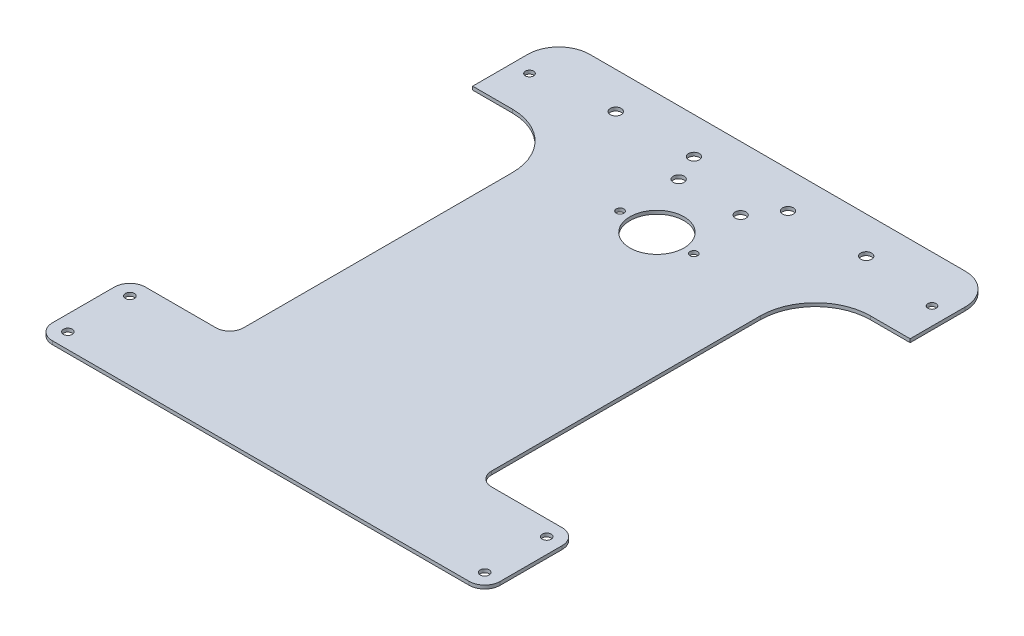
SolidWorks part; units mm, degrees
material "Thornel VCB-20 Carbon Cloth"
ref_plane "Front" through (0, 0, 0) normal (0, 0, 1) x (1, 0, 0)
ref_plane "Top" through (0, 0, 0) normal (0, 1, 0) x (1, 0, 0)
ref_plane "Right" through (0, 0, 0) normal (1, 0, 0) x (0, 0, -1)
ref_axis "X" through (-80.9, 0, 0) along (1, 0, 0)
ref_axis "Y" through (0, -50, 0) along (0, 1, 0)
ref_axis "Z" through (0, 0, -80.9) along (0, 0, 1)
sketch "Sketch1" plane through (0, 0, 0) normal (0, 1, 0) x (1, 0, 0)
  line L0 (-65, -150) -> (65, -150)
  line L1 (-65, -150) -> (-65, -123)
  line L2 (-65, -123) -> (-36, -123)
  line L3 (-36, -123) -> (-36, -25)
  line L4 (-36, -25) -> (-63.5, -25)
  line L5 (-63.5, -25) -> (-63.5, 0)
  line L6 (-63.5, 0) -> (63.5, 0)
  line L7 (63.5, 0) -> (63.5, -25)
  line L8 (63.5, -25) -> (36, -25)
  line L9 (36, -25) -> (36, -123)
  line L10 (36, -123) -> (65, -123)
  line L11 (65, -123) -> (65, -150)
  line L12 (0, -150) -> (0, 0) construction
  dimension "D1" = 130
  dimension "D2" = 72
  dimension "D5" = 25
  dimension "D6" = 127
  dimension "D7" = 150
  dimension "D3" = 27
  dimension "D4" = 90
extrude "Boss-Extrude1" add sketch "Sketch1" along normal mid plane 1
hole_wizard "M2 Clearance Hole1" positions "Sketch2" profile "Sketch3" hole size "M2" standard "ANSI Metric" end condition up to next
sketch "Sketch2" plane through (0, 0.5, 0) normal (0, 1, 0) x (1, 0, 0)
  line L0 (-60.5, -145.5) -> (60.5, -145.5) construction
  line L2 (-65, -150) -> (65, -150) construction
  line L3 (-65, -123) -> (-65, -150) construction
  line L4 (65, -150) -> (65, -123) construction
  line L5 (-60.5, -127.5) -> (-60.5, -145.5) construction
  line L8 (60.5, -127.5) -> (60.5, -145.5) construction
  point P0 (-60.5, -145.5)
  point P2 (60.5, -145.5)
  point P15 (-60.5, -127.5)
  point P17 (60.5, -127.5)
  dimension "D1" = 4.5
  dimension "D2" = 4.5
  dimension "D3" = 4.5
  dimension "D4" = 18
sketch "Sketch3" plane through (-60.5, 0.5, 145.5) normal (1, 0, 0) x (0, 0, 1)
  line L0 (0, 0) -> (0, 1)
  line L1 (0, 1) -> (1.3, 1)
  line L2 (1.3, 1) -> (1.3, 0)
  line L5 (1.3, 0) -> (0, 0)
  line L11 (0, -6.35) -> (0, 107.95) construction
  dimension "Thru Hole Dia." = 2.6
  dimension "Thru Hole Depth" = 1
fillet "Fillet1" radius 4.5 4 edges at (65, 0, 150) (-65, 0, 150) (65, 0, 123) (-65, 0, 123)
fillet "Fillet2" radius 9 2 edges at (63.5, 0, 0) (-63.5, 0, 0)
hole_wizard "M2 Clearance Hole2" positions "Sketch7" profile "Sketch8" hole size "M2" standard "ANSI Metric" end condition up to next
sketch "Sketch7" plane through (0, 0.5, 0) normal (0, 1, 0) x (1, 0, 0)
  line L0 (-58.42, -13.57) -> (58.42, -13.57) construction
  line L2 (0, 0) -> (0, -13.57) construction
  line L3 (54.5, 0) -> (-54.5, 0) construction
  line L5 (-63.5, -25) -> (-36, -25) construction
  point P0 (-58.42, -13.57)
  point P2 (58.42, -13.57)
  dimension "D1" = 116.84
  dimension "D2" = 11.43
sketch "Sketch8" plane through (-58.42, 0.5, 13.57) normal (1, 0, 0) x (0, 0, 1)
  line L0 (0, 0) -> (0, 1)
  line L1 (0, 1) -> (1.2, 1)
  line L2 (1.2, 1) -> (1.2, 0)
  line L5 (1.2, 0) -> (0, 0)
  line L11 (0, -6.35) -> (0, 107.95) construction
  dimension "Thru Hole Dia." = 2.4
  dimension "Thru Hole Depth" = 1
fillet "Fillet4" radius 4 2 edges at (36, 0, 123) (-36, 0, 123)
fillet "Fillet5" radius 16 2 edges at (36, 0, 25) (-36, 0, 25)
sketch "Sketch13" plane through (0, 0.5, 0) normal (0, 1, 0) x (1, 0, 0)
  line L0 (-38, -131) -> (-38, -142) construction
  line L1 (-35, -131) -> (-35, -142)
  line L3 (38, -131) -> (38, -142) construction
  line L5 (35, -131) -> (35, -142)
  line L6 (-38, -136.5) -> (38, -136.5) construction
  line L7 (0, -136.5) -> (0, 0) construction
  line L8 (54.5, 0) -> (-54.5, 0) construction
  line L11 (-60.5, -127.5) -> (-60.5, -145.5) construction
  line L12 (-60.5, -136.5) -> (-38, -136.5) construction
  line L13 (-38, -128) -> (-45.5, -128)
  line L14 (-38, -145) -> (-45.5, -145)
  line L15 (38, -128) -> (45.5, -128)
  line L16 (38, -145) -> (45.5, -145)
  line L17 (48.5, -131) -> (48.5, -142)
  line L18 (-48.5, -131) -> (-48.5, -142)
  line L19 (-35, -136.5) -> (-48.5, -136.5) construction
  line L20 (35, -136.5) -> (48.5, -136.5) construction
  arc A0 (-35, -131) -> (-38, -128) centre (-38, -131) ccw
  arc A1 (-38, -145) -> (-35, -142) centre (-38, -142) ccw
  arc A2 (38, -128) -> (35, -131) centre (38, -131) ccw
  arc A3 (35, -142) -> (38, -145) centre (38, -142) ccw
  circle A4 centre (-60.5, -127.5) radius 1.3 construction
  arc A5 (45.5, -128) -> (48.5, -131) centre (45.5, -131) cw
  arc A6 (48.5, -142) -> (45.5, -145) centre (45.5, -142) cw
  arc A7 (-45.5, -128) -> (-48.5, -131) centre (-45.5, -131) ccw
  arc A8 (-48.5, -142) -> (-45.5, -145) centre (-45.5, -142) ccw
  point P2 (-38, -136.5)
  point P8 (38, -136.5)
  dimension "D5" = 3.5
  dimension "D1" = 17
  dimension "D2" = 13.5
  dimension "D3" = 70
extrude "Cut-Extrude4" [suppressed] cut sketch "Sketch13" against normal through all
hole_wizard "M2 Clearance Hole3" positions "Sketch14" profile "Sketch15" hole size "M2" standard "ANSI Metric" end condition up to next
sketch "Sketch14" plane through (0, 0.5, 0) normal (0, 1, 0) x (1, 0, 0)
  line L2 (-10.7, -35) -> (10.7, -35) construction
  line L3 (0, 0) -> (0, -35) construction
  line L4 (54.5, 0) -> (-54.5, 0) construction
  point P0 (-10.7, -35)
  point P2 (10.7, -35)
  dimension "D1" = 21.4
  dimension "D2" = 35
sketch "Sketch15" plane through (-10.7, 0.5, 35) normal (1, 0, 0) x (0, 0, 1)
  line L0 (0, 0) -> (0, 1)
  line L1 (0, 1) -> (1.1, 1)
  line L2 (1.1, 1) -> (1.1, 0)
  line L5 (1.1, 0) -> (0, 0)
  line L11 (0, -6.35) -> (0, 107.95) construction
  dimension "Thru Hole Dia." = 2.2
  dimension "Thru Hole Depth" = 1
sketch "Sketch17" plane through (0, 0.5, 0) normal (0, 1, 0) x (1, 0, 0)
  line L0 (-36.35, -10.6) -> (-13.65, -10.6) construction
  line L1 (-13.65, -10.6) -> (13.65, -10.6) construction
  line L2 (13.65, -10.6) -> (36.35, -10.6) construction
  line L3 (7.8, -18.5) -> (-10.2, -18.5) construction
  line L4 (0, -10.6) -> (0, 0) construction
  line L5 (-25, -10.6) -> (-25, -15.252) construction
  line L6 (0, -10.6) -> (0, -18.5) construction
  line L7 (54.5, 0) -> (-54.5, 0) construction
  line L8 (25, -10.6) -> (25, -14.0507) construction
  circle A2 centre (7.8, -18.5) radius 1.575
  circle A3 centre (-10.2, -18.5) radius 1.575
  circle A8 centre (36.35, -10.6) radius 1.575
  circle A9 centre (13.65, -10.6) radius 1.575
  circle A10 centre (-13.65, -10.6) radius 1.575
  circle A11 centre (-36.35, -10.6) radius 1.575
  point P22 (-1.2, -18.5)
  dimension "D7" = 3.15
  dimension "D1" = 22.7
  dimension "D2" = 50
  dimension "D4" = 10.6
  dimension "D5" = 18.5
  dimension "D6" = 1.2
  dimension "D8" = 18
extrude "Cut-Extrude6" cut sketch "Sketch17" against normal through all
sketch "Sketch18" plane through (0, 0.5, 0) normal (0, 1, 0) x (1, 0, 0)
  line L0 (-10.7, -35) -> (10.7, -35) construction
  circle A0 centre (0, -35) radius 7.85
  circle A6 centre (-10.7, -35) radius 1.1 construction
  circle A8 centre (10.7, -35) radius 1.1 construction
  dimension "D3" = 15.7
extrude "Cut-Extrude7" cut sketch "Sketch18" against normal up to next
equation "\"D1@Sketch1\"=92+38"
